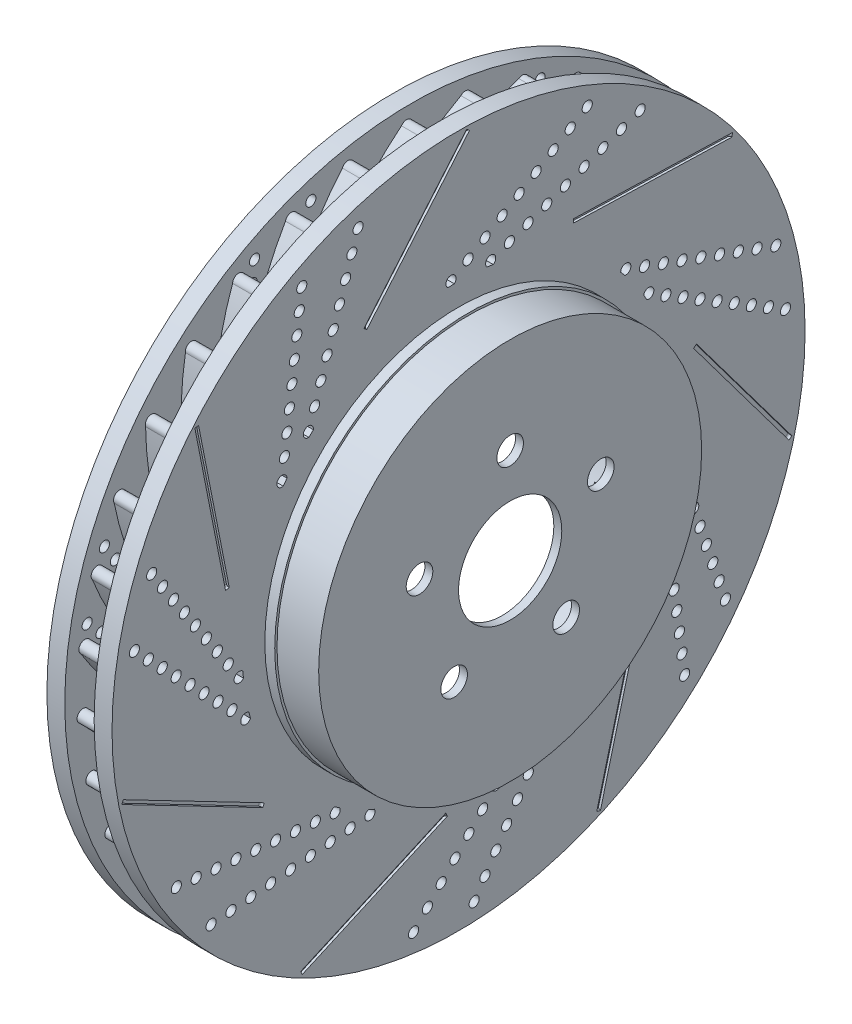
SolidWorks part; units mm, degrees
ref_plane "Front Plane" through (0, 0, 0) normal (0, 0, 1) x (1, 0, 0)
ref_plane "Top Plane" through (0, 0, 0) normal (0, 1, 0) x (1, 0, 0)
ref_plane "Right Plane" through (0, 0, 0) normal (1, 0, 0) x (0, 0, -1)
sketch "Sketch1" plane through (0, 0, 0) normal (1, 0, 0) x (0, 0, -1)
  circle A0 centre (0, 0) radius 87.27
  dimension "D1" = 174.54
extrude "Boss-Extrude1" add sketch "Sketch1" along normal blind 4.5
sketch "Sketch2" plane through (4.5, 0, 0) normal (1, 0, 0) x (0, 0, -1)
  circle A0 centre (0, 0) radius 49.72
  dimension "D1" = 99.44
extrude "Cut-Extrude1" cut sketch "Sketch2" against normal through all
sketch "Sketch4" plane through (4.5, 0, 0) normal (1, 0, 0) x (0, 0, -1)
  line L0 (0, 0) -> (0, -87.27) construction
  line L1 (-22.32, -50.7212) -> (-67.5581, -55.2445) construction
  line L2 (-31.0722, -45.884) -> (-76.684, -41.6607) construction
  circle A0 centre (0, 0) radius 55.415 construction
  circle A1 centre (0, 0) radius 87.27 construction
  circle A2 centre (-22.32, -50.7212) radius 1.28
  circle A3 centre (-31.0722, -45.884) radius 1.28
  circle A4 centre (-36.0722, -45.421) radius 1.28
  circle A5 centre (-46.0722, -44.4951) radius 1.28
  circle A6 centre (-61.0722, -43.1062) radius 1.28
  circle A7 centre (-41.0722, -44.9581) radius 1.28
  circle A8 centre (-66.0722, -42.6433) radius 1.28
  circle A9 centre (-51.0722, -44.0322) radius 1.28
  circle A10 centre (-56.0722, -43.5692) radius 1.28
  circle A11 centre (-71.0722, -42.1803) radius 1.28
  circle A12 centre (-27.32, -51.2211) radius 1.28
  circle A13 centre (-32.32, -51.7211) radius 1.28
  circle A14 centre (-37.32, -52.221) radius 1.28
  circle A15 centre (-42.32, -52.721) radius 1.28
  circle A16 centre (-47.32, -53.2209) radius 1.28
  circle A17 centre (-52.32, -53.7209) radius 1.28
  circle A18 centre (-57.32, -54.2208) radius 1.28
  circle A19 centre (-62.32, -54.7208) radius 1.28
  dimension "D1" = 110.83
  dimension "D2" = 2.56
  dimension "D3" = 10
  dimension "D4" = 22.32
  dimension "D7" = 5
  dimension "D8" = 5
  dimension "D9" = 5
  dimension "D10" = 5
  dimension "D11" = 5
  dimension "D12" = 5
  dimension "D13" = 5
  dimension "D14" = 5
  dimension "D15" = 5
  dimension "D16" = 5
  dimension "D17" = 5
  dimension "D18" = 5
  dimension "D19" = 5
  dimension "D20" = 5
  dimension "D21" = 5
  dimension "D22" = 5
  dimension "D5" = 84.29
  dimension "D6" = 95.29
extrude "Cut-Extrude2" cut sketch "Sketch4" against normal through all
pattern_circular "CirPattern1" count 7 over 360 about axis through (4.5, 0, 0) along (1, 0, 0) of "Cut-Extrude2"
sketch "Sketch8" plane through (4.5, 0, 0) normal (1, 0, 0) x (0, 0, -1)
  line L0 (0, 0) -> (0, -87.27) construction
  line L1 (-3.2223, -59.9684) -> (-39.7642, -76.2379)
  line L2 (-3.2223, -59.9684) -> (-2.84, -60.8272)
  line L3 (-39.7642, -76.2379) -> (-39.3818, -77.0966)
  line L4 (-2.84, -60.8272) -> (-39.3818, -77.0966)
  circle A0 centre (0, 0) radius 87.27 construction
  dimension "D1" = 2.84
  dimension "D2" = 66
  dimension "D3" = 0.94
  dimension "D4" = 40
extrude "Cut-Extrude3" cut sketch "Sketch8" against normal blind 0.6
fillet "Fillet1" radius 0.6 2 edges at (3.9, -76.6672, 39.573) (3.9, -60.3978, 3.0312)
pattern_circular "CirPattern2" count 7 over 360 about axis through (4.5, 0, 0) along (1, 0, 0) of "Fillet1", "Cut-Extrude3"
ref_plane "Plane1" through (-3.7, 0, 0) normal (-1, 0, 0) x (0, 0, 1)
mirror "Mirror1" about plane through (-3.7, 0, 0) normal (-1, 0, 0) of bodies 106
sketch "Sketch9" plane through (-7.4, 0, 0) normal (1, 0, 0) x (0, 0, -1)
  line L0 (0, 0) -> (0, -87.27) construction
  line L1 (0, 0) -> (-87.27, 0) construction
  circle A0 centre (0, 0) radius 87.27 construction
  arc A1 (-75.3853, -32.1145) -> (-75.9062, -35.1369) centre (-75.6458, -33.6257) ccw
  circle A2 centre (0, 0) radius 49.72 construction
  arc A3 (-68.4396, -45.059) -> (-68.4124, -48.1258) centre (-68.426, -46.5924) ccw
  arc A4 (-22.4933, -44.3411) -> (-20.4692, -45.311) centre (0, 0) ccw
  arc A5 (-30.0492, -39.6122) -> (-28.2309, -40.9279) centre (0, 0) ccw
  arc A6 (-79.9081, -18.1378) -> (-80.9603, -21.0186) centre (-80.4342, -19.5782) ccw
  arc A7 (-36.6393, -33.6101) -> (-35.0851, -35.2294) centre (0, 0) ccw
  arc A8 (-81.8626, -3.5782) -> (-83.4122, -6.2248) centre (-82.6374, -4.9015) ccw
  arc A9 (-42.0518, -26.5278) -> (-40.8118, -28.3986) centre (0, 0) ccw
  arc A10 (-81.1859, 11.0964) -> (-83.1833, 8.769) centre (-82.1846, 9.9327) ccw
  arc A11 (-46.1128, -18.5928) -> (-45.2267, -20.655) centre (0, 0) ccw
  arc A12 (-77.8999, 25.4144) -> (-80.2807, 23.4811) centre (-79.0903, 24.4477) ccw
  arc A13 (-48.6916, -10.0603) -> (-48.1879, -12.2475) centre (0, 0) ccw
  arc A14 (-72.1101, 38.9155) -> (-74.7979, 37.4384) centre (-73.454, 38.177) ccw
  arc A15 (-49.7054, -1.2044) -> (-49.6004, -3.4464) centre (0, 0) ccw
  arc A16 (-64.0026, 51.1659) -> (-66.9109, 50.1924) centre (-65.4568, 50.6792) ccw
  arc A17 (-49.1217, 7.6902) -> (-49.4187, 5.4655) centre (0, 0) ccw
  arc A18 (-53.838, 61.7718) -> (-56.8735, 61.3332) centre (-55.3558, 61.5525) ccw
  arc A19 (-46.9591, 16.3377) -> (-47.6486, 14.2017) centre (0, 0) ccw
  arc A20 (-41.9431, 70.3922) -> (-45.008, 70.5027) centre (-43.4755, 70.4475) ccw
  arc A21 (-43.2873, 24.46) -> (-44.3471, 22.4815) centre (0, 0) ccw
  arc A22 (-28.7, 76.7502) -> (-31.696, 77.4062) centre (-30.198, 77.0782) ccw
  arc A23 (-38.2241, 31.7961) -> (-39.6202, 30.0387) centre (0, 0) ccw
  arc A24 (-14.5345, 80.6414) -> (-17.3652, 81.8218) centre (-15.9499, 81.2316) ccw
  arc A25 (-31.9324, 38.1103) -> (-33.6198, 36.6304) centre (0, 0) ccw
  arc A26 (0.0981, 81.9407) -> (-2.4763, 83.6075) centre (-1.1891, 82.7741) ccw
  arc A27 (-24.6144, 43.1996) -> (-26.5389, 42.0448) centre (0, 0) ccw
  arc A28 (14.7276, 80.6063) -> (12.4922, 82.7061) centre (13.6099, 81.6562) ccw
  arc A29 (-16.5052, 46.9005) -> (-18.6051, 46.1078) centre (0, 0) ccw
  arc A30 (28.8838, 76.6812) -> (27.0592, 79.1464) centre (27.9715, 77.9138) ccw
  arc A31 (-7.8656, 49.0939) -> (-10.0732, 48.6889) centre (0, 0) ccw
  arc A32 (42.1116, 70.2916) -> (40.7565, 73.0429) centre (41.434, 71.6672) ccw
  arc A33 (1.0269, 49.7094) -> (-1.2176, 49.7051) centre (0, 0) ccw
  arc A34 (53.9859, 61.6426) -> (53.1438, 64.5917) centre (53.5648, 63.1172) ccw
  arc A35 (9.8863, 48.7272) -> (7.6772, 49.1237) centre (0, 0) ccw
  arc A36 (64.125, 51.0125) -> (63.8231, 54.0645) centre (63.974, 52.5385) ccw
  arc A37 (18.428, 46.1789) -> (16.3252, 46.9635) centre (0, 0) ccw
  arc A38 (72.2031, 38.7427) -> (72.451, 41.7996) centre (72.327, 40.2712) ccw
  arc A39 (26.3774, 42.1463) -> (24.4485, 43.2938) centre (0, 0) ccw
  arc A40 (77.9606, 25.2277) -> (78.7503, 28.1912) centre (78.3554, 26.7095) ccw
  arc A41 (33.479, 36.7591) -> (31.786, 38.2326) centre (0, 0) ccw
  arc A42 (81.2123, 10.9019) -> (82.5185, 13.6768) centre (81.8654, 12.2894) ccw
  arc A43 (39.5046, 30.1905) -> (38.1018, 31.9426) centre (0, 0) ccw
  arc A44 (81.8538, -3.7743) -> (83.6344, -1.2772) centre (82.7441, -2.5258) ccw
  arc A45 (44.2605, 22.6515) -> (43.1931, 24.6259) centre (0, 0) ccw
  arc A46 (79.8644, -18.3292) -> (82.0623, -16.1902) centre (80.9634, -17.2597) ccw
  arc A47 (47.5938, 14.3844) -> (46.8961, 16.5177) centre (0, 0) ccw
  arc A48 (75.3082, -32.295) -> (77.8527, -30.5828) centre (76.5804, -31.4389) ccw
  arc A49 (49.3974, 5.6551) -> (49.0918, 7.8787) centre (0, 0) ccw
  arc A50 (68.3314, -45.2228) -> (71.1408, -43.9925) centre (69.7361, -44.6076) ccw
  arc A51 (49.6133, -3.256) -> (49.7097, -1.0136) centre (0, 0) ccw
  arc A52 (59.1585, -56.6971) -> (62.1424, -55.9882) centre (60.6504, -56.3426) ccw
  arc A53 (48.2346, -12.0625) -> (48.7298, -9.8734) centre (0, 0) ccw
  arc A54 (48.0841, -66.3491) -> (51.1466, -66.1844) centre (49.6154, -66.2667) ccw
  arc A55 (45.3056, -20.4813) -> (46.1838, -18.4157) centre (0, 0) ccw
  arc A56 (35.4643, -73.8686) -> (38.507, -74.2534) centre (36.9857, -74.061) ccw
  arc A57 (40.9204, -28.2417) -> (42.1533, -26.3662) centre (0, 0) ccw
  arc A58 (21.7046, -79.0139) -> (24.6297, -79.9358) centre (23.1672, -79.4748) ccw
  arc A59 (35.2201, -35.0945) -> (36.768, -33.4693) centre (0, 0) ccw
  arc A60 (7.2474, -81.6196) -> (9.9608, -83.049) centre (8.6041, -82.3343) ccw
  arc A61 (28.3877, -40.8193) -> (30.201, -39.4966) centre (0, 0) ccw
  arc A62 (-7.4429, -81.602) -> (-5.0282, -83.4929) centre (-6.2355, -82.5475) ccw
  arc A63 (20.6429, -45.2322) -> (22.6632, -44.2544) centre (0, 0) ccw
  arc A64 (-21.8938, -78.9617) -> (-19.8556, -81.2533) centre (-20.8747, -80.1075) ccw
  arc A65 (12.2347, -48.1912) -> (14.3971, -47.5899) centre (0, 0) ccw
  arc A66 (-35.6412, -73.7834) -> (-34.0449, -76.4022) centre (-34.843, -75.0928) ccw
  arc A67 (3.4332, -49.6013) -> (5.6682, -49.3958) centre (0, 0) ccw
  arc A68 (-48.2429, -66.2337) -> (-47.1399, -69.0954) centre (-47.6914, -67.6646) ccw
  arc A69 (-5.4786, -49.4172) -> (-3.2428, -49.6141) centre (0, 0) ccw
  arc A70 (-59.2941, -56.5552) -> (-58.7198, -59.5679) centre (-59.007, -58.0616) ccw
  arc A71 (-14.2144, -47.6448) -> (-12.0497, -48.2378) centre (0, 0) ccw
  spline S0 degree 2 poles (-20.4692, -45.311) (-43.2018, -55.96) (-68.4124, -48.1258) knots 0 0 0 1 1 1
  spline S1 degree 2 poles (-22.4933, -44.3411) (-44.1636, -54.5616) (-68.4396, -45.059) knots 0 0 0 1 1 1
  spline S2 degree 2 poles (-30.0492, -39.6122) (-53.1962, -45.7991) (-75.3853, -32.1145) knots 0 0 0 1 1 1
  spline S3 degree 2 poles (-28.2309, -40.9279) (-52.4996, -47.3467) (-75.9062, -35.1369) knots 0 0 0 1 1 1
  spline S4 degree 2 poles (-36.6393, -33.6101) (-60.5191, -35.5645) (-79.9081, -18.1378) knots 0 0 0 1 1 1
  spline S5 degree 2 poles (-35.0851, -35.2294) (-60.11, -37.2117) (-80.9603, -21.0186) knots 0 0 0 1 1 1
  spline S6 degree 2 poles (-42.0518, -26.5278) (-65.8968, -24.1869) (-81.8626, -3.5782) knots 0 0 0 1 1 1
  spline S7 degree 2 poles (-40.8118, -28.3986) (-65.7884, -25.8806) (-83.4122, -6.2248) knots 0 0 0 1 1 1
  spline S8 degree 2 poles (-46.1128, -18.5928) (-69.1565, -12.0318) (-81.1859, 11.0964) knots 0 0 0 1 1 1
  spline S9 degree 2 poles (-45.2267, -20.655) (-69.3523, -13.7177) (-83.1833, 8.769) knots 0 0 0 1 1 1
  spline S10 degree 2 poles (-48.6916, -10.0603) (-70.1935, 0.5099) (-77.8999, 25.4144) knots 0 0 0 1 1 1
  spline S11 degree 2 poles (-48.1879, -12.2475) (-70.6872, -1.114) (-80.2807, 23.4811) knots 0 0 0 1 1 1
  spline S12 degree 2 poles (-49.7054, -1.2044) (-68.9745, 13.0352) (-72.1101, 38.9155) knots 0 0 0 1 1 1
  spline S13 degree 2 poles (-49.6004, -3.4464) (-69.7501, 11.5256) (-74.7979, 37.4384) knots 0 0 0 1 1 1
  spline S14 degree 2 poles (-49.1217, 7.6902) (-65.5385, 25.1416) (-64.0026, 51.1659) knots 0 0 0 1 1 1
  spline S15 degree 2 poles (-49.4187, 5.4655) (-66.5712, 23.7948) (-66.9109, 50.1924) knots 0 0 0 1 1 1
  spline S16 degree 2 poles (-46.9591, 16.3377) (-59.996, 36.4399) (-53.838, 61.7718) knots 0 0 0 1 1 1
  spline S17 degree 2 poles (-47.6486, 14.2017) (-61.2527, 35.2991) (-56.8735, 61.3332) knots 0 0 0 1 1 1
  spline S18 degree 2 poles (-43.2873, 24.46) (-52.5253, 46.567) (-41.9431, 70.3922) knots 0 0 0 1 1 1
  spline S19 degree 2 poles (-44.3471, 22.4815) (-53.9654, 45.669) (-45.008, 70.5027) knots 0 0 0 1 1 1
  spline S20 degree 2 poles (-38.2241, 31.7961) (-43.3663, 55.1974) (-28.7, 76.7502) knots 0 0 0 1 1 1
  spline S21 degree 2 poles (-39.6202, 30.0387) (-44.9437, 54.5709) (-31.696, 77.4062) knots 0 0 0 1 1 1
  spline S22 degree 2 poles (-31.9324, 38.1103) (-32.8135, 62.0537) (-14.5345, 80.6414) knots 0 0 0 1 1 1
  spline S23 degree 2 poles (-33.6198, 36.6304) (-34.4774, 61.719) (-17.3652, 81.8218) knots 0 0 0 1 1 1
  spline S24 degree 2 poles (-24.6144, 43.1996) (-21.2061, 66.9156) (0.0981, 81.9407) knots 0 0 0 1 1 1
  spline S25 degree 2 poles (-26.5389, 42.0448) (-22.903, 66.8833) (-2.4763, 83.6075) knots 0 0 0 1 1 1
  spline S26 degree 2 poles (-16.5052, 46.9005) (-8.917, 69.6267) (14.7276, 80.6063) knots 0 0 0 1 1 1
  spline S27 degree 2 poles (-18.6051, 46.1078) (-10.5925, 69.8979) (12.4922, 82.7061) knots 0 0 0 1 1 1
  spline S28 degree 2 poles (-7.8656, 49.0939) (3.6586, 70.1) (28.8838, 76.6812) knots 0 0 0 1 1 1
  spline S29 degree 2 poles (-10.0732, 48.6889) (2.0585, 70.666) (27.0592, 79.1464) knots 0 0 0 1 1 1
  spline S30 degree 2 poles (1.0269, 49.7094) (16.1166, 68.3202) (42.1116, 70.2916) knots 0 0 0 1 1 1
  spline S31 degree 2 poles (-1.2176, 49.7051) (14.6434, 69.1628) (40.7565, 73.0429) knots 0 0 0 1 1 1
  spline S32 degree 2 poles (9.8863, 48.7272) (28.0567, 64.3445) (53.9859, 61.6426) knots 0 0 0 1 1 1
  spline S33 degree 2 poles (7.6772, 49.1237) (26.7575, 65.4367) (53.1438, 64.5917) knots 0 0 0 1 1 1
  spline S34 degree 2 poles (18.428, 46.1789) (39.095, 58.3007) (64.125, 51.0125) knots 0 0 0 1 1 1
  spline S35 degree 2 poles (16.3252, 46.9635) (38.0117, 59.6073) (63.8231, 54.0645) knots 0 0 0 1 1 1
  spline S36 degree 2 poles (26.3774, 42.1463) (48.8767, 50.3832) (72.2031, 38.7427) knots 0 0 0 1 1 1
  spline S37 degree 2 poles (24.4485, 43.2938) (48.0441, 51.8622) (72.451, 41.7996) knots 0 0 0 1 1 1
  spline S38 degree 2 poles (33.479, 36.7591) (57.0875, 40.8462) (77.9606, 25.2277) knots 0 0 0 1 1 1
  spline S39 degree 2 poles (31.786, 38.2326) (56.5324, 42.4501) (78.7503, 28.1912) knots 0 0 0 1 1 1
  spline S40 degree 2 poles (39.5046, 30.1905) (63.4634, 29.9964) (81.2123, 10.9019) knots 0 0 0 1 1 1
  spline S41 degree 2 poles (38.1018, 31.9426) (63.2036, 31.6737) (82.5185, 13.6768) knots 0 0 0 1 1 1
  spline S42 degree 2 poles (44.2605, 22.6515) (67.7996, 18.1825) (81.8538, -3.7743) knots 0 0 0 1 1 1
  spline S43 degree 2 poles (43.1931, 24.6259) (67.8435, 19.8792) (83.6344, -1.2772) knots 0 0 0 1 1 1
  spline S44 degree 2 poles (47.5938, 14.3844) (69.9567, 5.7843) (79.8644, -18.3292) knots 0 0 0 1 1 1
  spline S45 degree 2 poles (46.8961, 16.5177) (70.3028, 7.4458) (82.0623, -16.1902) knots 0 0 0 1 1 1
  spline S46 degree 2 poles (49.3974, 5.6551) (69.8653, -6.7999) (75.3082, -32.295) knots 0 0 0 1 1 1
  spline S47 degree 2 poles (49.0918, 7.8787) (70.5025, -5.2269) (77.8527, -30.5828) knots 0 0 0 1 1 1
  spline S48 degree 2 poles (49.6133, -3.256) (67.5283, -19.1656) (68.3314, -45.2228) knots 0 0 0 1 1 1
  spline S49 degree 2 poles (49.7097, -1.0136) (68.4362, -17.7316) (71.1408, -43.9925) knots 0 0 0 1 1 1
  spline S50 degree 2 poles (48.2346, -12.0625) (63.021, -30.9152) (59.1585, -56.6971) knots 0 0 0 1 1 1
  spline S51 degree 2 poles (48.7298, -9.8734) (64.1703, -29.6664) (62.1424, -55.9882) knots 0 0 0 1 1 1
  spline S52 degree 2 poles (45.3056, -20.4813) (56.4881, -41.6712) (48.0841, -66.3491) knots 0 0 0 1 1 1
  spline S53 degree 2 poles (46.1838, -18.4157) (57.8419, -40.6477) (51.1466, -66.1844) knots 0 0 0 1 1 1
  spline S54 degree 2 poles (40.9204, -28.2417) (48.1396, -51.0879) (35.4643, -73.8686) knots 0 0 0 1 1 1
  spline S55 degree 2 poles (42.1533, -26.3662) (49.6544, -50.3225) (38.507, -74.2534) knots 0 0 0 1 1 1
  spline S56 degree 2 poles (35.2201, -35.0945) (38.2439, -58.8626) (21.7046, -79.0139) knots 0 0 0 1 1 1
  spline S57 degree 2 poles (36.768, -33.4693) (39.871, -58.38) (24.6297, -79.9358) knots 0 0 0 1 1 1
  spline S58 degree 2 poles (28.3877, -40.8193) (27.119, -64.7453) (7.2474, -81.6196) knots 0 0 0 1 1 1
  spline S59 degree 2 poles (30.201, -39.4966) (28.8062, -64.561) (9.9608, -83.049) knots 0 0 0 1 1 1
  spline S60 degree 2 poles (20.6429, -45.2322) (15.1224, -68.5471) (-7.4429, -81.602) knots 0 0 0 1 1 1
  spline S61 degree 2 poles (22.6632, -44.2544) (16.8154, -68.667) (-5.0282, -83.4929) knots 0 0 0 1 1 1
  spline S62 degree 2 poles (12.2347, -48.1912) (2.6398, -70.1457) (-21.8938, -78.9617) knots 0 0 0 1 1 1
  spline S63 degree 2 poles (14.3971, -47.5899) (4.2842, -70.566) (-19.8556, -81.2533) knots 0 0 0 1 1 1
  spline S64 degree 2 poles (3.4332, -49.6013) (-9.9276, -69.4898) (-35.6412, -73.7834) knots 0 0 0 1 1 1
  spline S65 degree 2 poles (5.6682, -49.3958) (-8.3847, -70.197) (-34.0449, -76.4022) knots 0 0 0 1 1 1
  spline S66 degree 2 poles (-5.4786, -49.4172) (-22.1759, -66.6005) (-48.2429, -66.2337) knots 0 0 0 1 1 1
  spline S67 degree 2 poles (-3.2428, -49.6141) (-20.7841, -67.5718) (-47.1399, -69.0954) knots 0 0 0 1 1 1
  spline S68 degree 2 poles (-14.2144, -47.6448) (-33.7115, -61.5705) (-59.2941, -56.5552) knots 0 0 0 1 1 1
  spline S69 degree 2 poles (-12.0497, -48.2378) (-32.5155, -62.7747) (-58.7198, -59.5679) knots 0 0 0 1 1 1
  point P255 (0, 0)
  dimension "D1" = 35
extrude "Boss-Extrude2" add sketch "Sketch9" along normal blind 7
sketch "Sketch12" plane through (-11.9, 0, 0) normal (-1, 0, 0) x (0, 0, 1)
  circle A0 centre (0, 0) radius 53.345
  dimension "D1" = 106.69
extrude "Cut-Extrude5" cut sketch "Sketch12" against normal blind 4.5
sketch "Sketch13" plane through (0, 0, 0) normal (0, 1, 0) x (1, 0, 0)
  line L0 (0, 0) -> (42.5611, 0) construction
  line L1 (0, 54.4162) -> (4.5, 54.4162)
  line L2 (0, 55.6962) -> (0, 53.1362) construction
  line L3 (4.5, 53.1362) -> (4.5, 55.6962) construction
  line L4 (0, 54.4162) -> (0, 44.4)
  line L5 (0, 44.4) -> (22.0128, 44.4) construction
  line L6 (15.4922, 43.859) -> (15.4922, 0)
  line L7 (0, 49.72) -> (0, -49.72) construction
  line L8 (4.5, 54.4162) -> (4.5, 48.7971)
  line L9 (15.4922, 0) -> (17.4922, 0)
  line L10 (4.5, -49.72) -> (4.5, 49.72) construction
  line L12 (0, 44.4) -> (15.4922, 43.859)
  line L13 (17.4922, 0) -> (17.4922, 48.2247)
  line L14 (17.4922, 48.2247) -> (42.5611, 48.2247) construction
  line L15 (4.5, 48.7971) -> (7.0004, 48.7971)
  line L16 (7.0004, 48.7971) -> (7.0004, 48.2247)
  line L17 (7.0004, 48.2247) -> (17.4922, 48.2247)
  dimension "D1" = 44.4
  dimension "D2" = 2
  dimension "D3" = 2
revolve "Revolve2" add sketch "Sketch13" angle 360 about L0
sketch "Sketch14" plane through (17.4922, 0, 0) normal (1, 0, 0) x (0, 0, -1)
  circle A0 centre (0, 0) radius 13
  circle A1 centre (0, 0) radius 24 construction
  circle A2 centre (0, 24) radius 3.35
  circle A3 centre (22.8254, 7.4164) radius 3.35
  circle A4 centre (14.1068, -19.4164) radius 3.35
  circle A5 centre (-14.1068, -19.4164) radius 3.35
  circle A6 centre (-22.8254, 7.4164) radius 3.35
  point P17 (0, 0)
  dimension "D1" = 26
  dimension "D2" = 48
  dimension "D3" = 6.7
  dimension "D4" = 5
extrude "Cut-Extrude6" cut sketch "Sketch14" against normal through all
